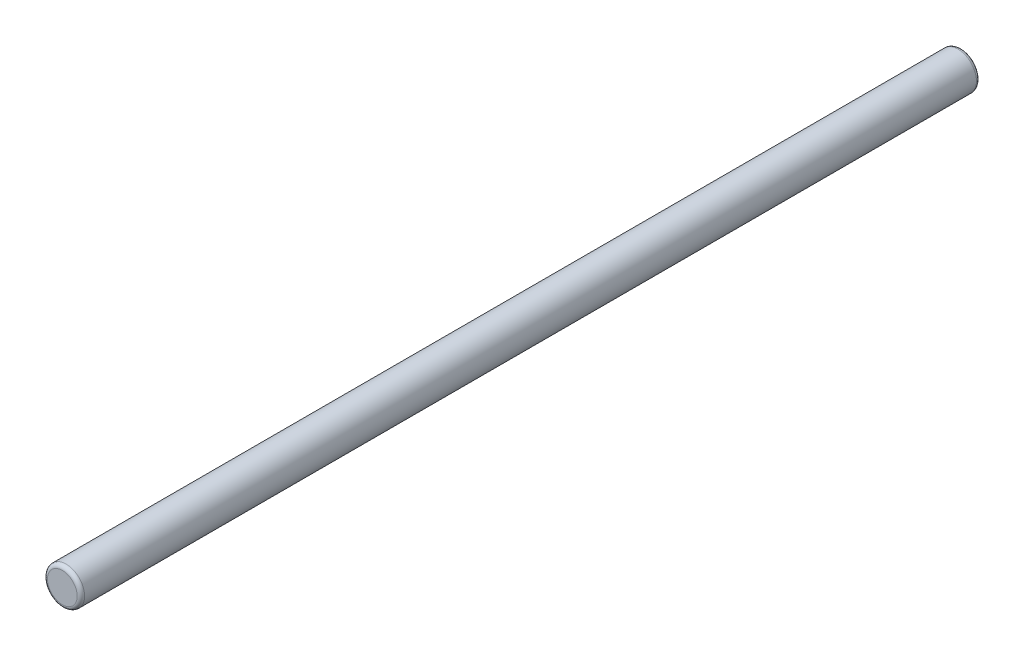
SolidWorks part; units mm, degrees
ref_plane "Plano frontal" through (0, 0, 0) normal (0, 0, 1) x (1, 0, 0)
ref_plane "Plano superior" through (0, 0, 0) normal (0, 1, 0) x (1, 0, 0)
ref_plane "Plano direito" through (0, 0, 0) normal (1, 0, 0) x (0, 0, -1)
sketch "Esboço1" plane through (0, 0, 0) normal (0, 0, 1) x (1, 0, 0)
  circle A0 centre (0, 0) radius 2.35
  dimension "D1" = 4.7
extrude "Ressalto-extrusão3" add sketch "Esboço1" along normal blind 113.94
fillet "Filete1" radius 0.47 2 edges at (2.35, 0, 0) (2.35, 0, 113.94)
